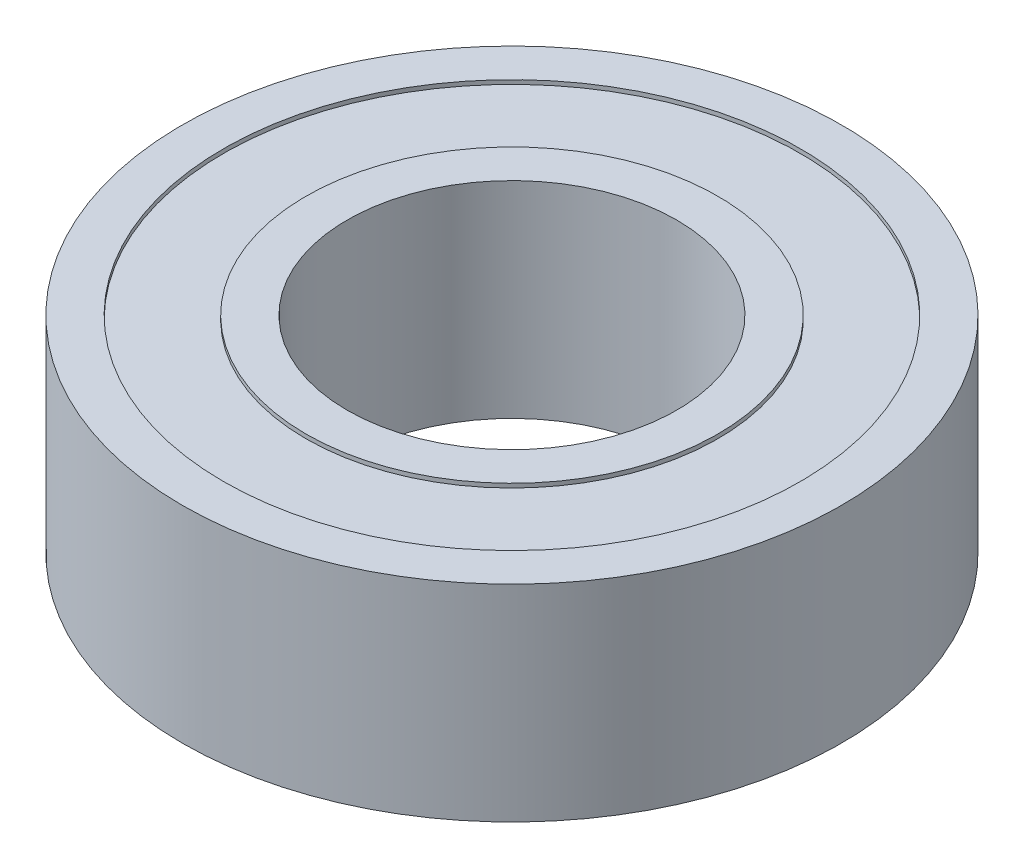
SolidWorks part; units mm, degrees
ref_plane "Front plane" through (0, 0, 0) normal (0, 0, 1) x (1, 0, 0)
ref_plane "Top plane" through (0, 0, 0) normal (0, 1, 0) x (1, 0, 0)
ref_plane "Right plane" through (0, 0, 0) normal (1, 0, 0) x (0, 0, -1)
ref_axis "Axis X" through (0, 0, 0) along (1, 0, 0)
ref_axis "Axis Y" through (0, 0, 0) along (0, 1, 0)
ref_axis "Axis Z" through (0, 0, 0) along (0, 0, 1)
sketch "Sketch1" plane through (0, 0, 0) normal (0, 1, 0) x (1, 0, 0)
  circle A0 centre (0, 0) radius 8
  circle A1 centre (0, 0) radius 4
  dimension "D1" = 16
  dimension "D2" = 8
extrude "Extrude1" add sketch "Sketch1" along normal blind 5
sketch "Sketch2" plane through (0, 5, 0) normal (0, 1, 0) x (1, 0, 0)
  circle A2 centre (0, 0) radius 7
  circle A3 centre (0, 0) radius 7
  circle A5 centre (0, 0) radius 5
  circle A6 centre (0, 0) radius 5
extrude "Extrude2" cut sketch "Sketch2" against normal blind 0.1
sketch "Sketch3" plane through (0, 0, 0) normal (0, -1, 0) x (1, 0, 0)
  circle A2 centre (0, 0) radius 7
  circle A3 centre (0, 0) radius 7
  circle A5 centre (0, 0) radius 5
  circle A6 centre (0, 0) radius 5
extrude "Extrude3" cut sketch "Sketch3" against normal blind 0.1
equation "\"motor_D\"= 40'Motor diameter"
equation "\"motor_H\"= 18'Motor heigh"
equation "\"motor_d1\"= 28'Seating diameter of screws on the fixed part of the motor"
equation "\"motor_s1\"= 3'Screws diameter on the fixed part of motor"
equation "\"motor_a2\"= 10'Seating parameter in rectangle of screws on the moving part of the motor"
equation "\"motor_s2\"= 3'Screws diameter on the moving part of motor"
equation "\"motor_Dc\"= 10'Central hole diameter of motor"
equation "\"bearing_d1\"= 8'Bearing inner diameter"
equation "\"bearing_d2\"= 16'Bearing external diameter"
equation "\"bearing h\"= 5'Bearing heigh"
equation "\"pin_d\"= 2'Pin diameter"
equation "\"pin_h\"= 12'Pin heigh"
equation "\"magnet_d1\"= 5'Magnet inner diameter"
equation "\"magnet_d2\"= 9.5'Magnet external diameter"
equation "\"magnet_h\"= 3'Magnet heigh"
equation "\"motor_b2\"= 22'Seating parameter in rectangle of screws on the moving part of the motor"
equation "\"motor_d2\"= 28'Seating diameter of screws on the moving part of the motor (if this parameter is not determine, write 0)"
equation "\"motor_cmd\"= 13'Central magnet mount diameter"
equation "\"motor_cmh\"= 0'Central magnet mount heigh (if not write 0)"
equation "\"motor_whR\"= 17.3'Distance from center of motor to wires"
equation "\"D1@Sketch1\"=\"bearing_d2\""
equation "\"D2@Sketch1\"=\"bearing_d1\""
equation "\"D1@Extrude1\"=\"bearing h\""
equation "\"D1@Sketch2\"=(\"bearing_d2\"-\"bearing_d1\")/2/4"
equation "\"D2@Sketch2\"=\"D1@Sketch2\""
equation "\"D1@Extrude2\"=0.1"
equation "\"D2@Sketch3\"=(\"bearing_d2\"-\"bearing_d1\")/2/4"
equation "\"D1@Sketch3\"=\"D2@Sketch3\""
